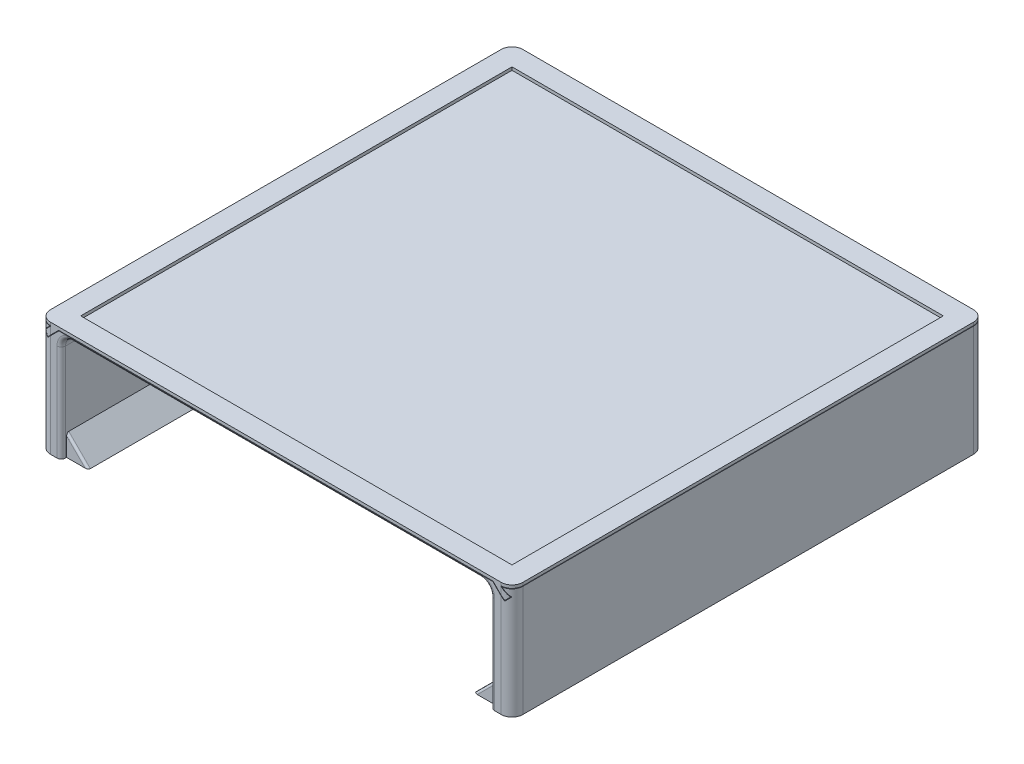
SolidWorks part; units mm, degrees
ref_plane "Front Plane" through (0, 0, 0) normal (0, 0, 1) x (1, 0, 0)
ref_plane "Top Plane" through (0, 0, 0) normal (0, 1, 0) x (1, 0, 0)
ref_plane "Right Plane" through (0, 0, 0) normal (1, 0, 0) x (0, 0, -1)
sketch "Sketch1" plane through (0, 0, 0) normal (0, 0, 1) x (1, 0, 0)
  line L0 (-99.5, -1.5) -> (99.5, -1.5)
  line L1 (-109.5, -51.5) -> (-99.5, -51.5)
  line L2 (-109.5, -51.5) -> (-109.5, 0)
  line L4 (-99.5, -51.5) -> (-99.5, -1.5)
  line L5 (0, -1.5) -> (0, 0) construction
  line L10 (-109.5, 0.2) -> (-104.2343, 0.2)
  line L14 (-100.6988, 0.2) -> (100.6988, 0.2)
  line L15 (0, 0.2) -> (0, 1.6) construction
  line L16 (109.5, 1.6) -> (-109.5, 1.6)
  line L17 (-109.5, 1.6) -> (-109.5, 0.2)
  line L21 (-109.5, 0) -> (-104.7172, 0)
  line L22 (-100.6159, 0) -> (100.6159, 0)
  line L23 (109.5, 1.2) -> (-109.5, 1.2) construction
  line L24 (109.5, 0) -> (104.7172, 0)
  line L28 (109.5, 1.6) -> (109.5, 0.2)
  line L29 (109.5, 0.2) -> (104.2343, 0.2)
  line L33 (99.5, -51.5) -> (99.5, -1.5)
  line L34 (109.5, -51.5) -> (109.5, 0)
  line L35 (109.5, -51.5) -> (99.5, -51.5)
  line L36 (-100.5, 0.2) -> (-100.5, 1.2) construction
  line L37 (-100.6988, 0.2) -> (-105.9494, -5.0506)
  line L38 (-105.9494, -5.0506) -> (-107.7172, -3.2828)
  line L39 (-107.7172, -3.2828) -> (-104.2343, 0.2)
  line L40 (-104.7172, 0) -> (-108, -3.2828)
  line L41 (-108, -3.2828) -> (-105.9494, -5.3335)
  line L42 (-105.9494, -5.3335) -> (-100.6159, 0)
  line L43 (-106.9747, -4.3081) -> (-106.8333, -4.1667) construction
  line L44 (100.6988, 0.2) -> (105.9494, -5.0506)
  line L45 (105.9494, -5.3335) -> (100.6159, 0)
  line L46 (108, -3.2828) -> (105.9494, -5.3335)
  line L47 (105.9494, -5.0506) -> (107.7172, -3.2828)
  line L48 (107.7172, -3.2828) -> (104.2343, 0.2)
  line L49 (104.7172, 0) -> (108, -3.2828)
  point P21 (0, 1.2)
  dimension "D1" = 109.5
  dimension "D5" = 0.2
  dimension "D9" = 0.4
  dimension "MetalSheetGap" = 1
  dimension "D11" = 10
  dimension "MainBoardSize" = 50
  dimension "D13" = 9
  dimension "D3" = 45
  dimension "D4" = 1.5
  dimension "D2" = 2.5
  dimension "D7" = 0.2
  dimension "D8" = 0.2
  dimension "D10" = 3
  dimension "D6" = 1.5
extrude "Boss-Extrude1" add sketch "Sketch1" along normal mid plane 219 contours L4 L0 L33 L35 L34 L24 L49 L46 L45 L22 L42 L41 L40 L21 L2 L1
extrude "Boss-Extrude2" add sketch "Sketch1<4>" along normal mid plane 219 separate body contours L16 L17 L10 L39 L38 L37 L14 L44 L47 L48 L29 L28
sketch "Sketch1<4>" plane through (0, 0, 0) normal (0, 0, 1) x (1, 0, 0) same geometry as "Sketch1"
sketch "Sketch2" plane through (0, 0.2, 0) normal (0, -1, 0) x (1, 0, 0)
  line L1 (-100, -100) -> (100, -100)
  line L2 (-100, -100) -> (-100, 100)
  line L3 (-100, 100) -> (100, 100)
  line L4 (100, -100) -> (100, 100)
  line L5 (-100, -100) -> (100, 100) construction
  line L6 (-100, 100) -> (100, -100) construction
  point P0 (0, 0)
  dimension "D1" = 200
  dimension "D2" = 200
extrude "Cut-Extrude1" cut sketch "Sketch2" against normal through all contours L3 L4 L1 L2
fillet "Fillet1" radius 5 2 edges at (99.5, -1.5, 0) (-99.5, -1.5, 0)
sketch "Sketch3" plane through (0, 0, 0) normal (0, 0, 1) x (1, 0, 0)
  line L1 (-99.5, -1.5) -> (99.5, -1.5)
  line L2 (-99.5, -1.5) -> (-99.5, -51.5)
  line L3 (-99.5, -51.5) -> (99.5, -51.5)
  line L4 (99.5, -1.5) -> (99.5, -51.5)
extrude "Boss-Extrude3" add sketch "Sketch3" along normal mid plane 10
fillet "Fillet2" radius 5 4 edges at (-109.5, -25.75, 109.5) (-109.5, -25.75, -109.5) (109.5, -25.75, -109.5) (109.5, -25.75, 109.5)
sketch "Sketch9" plane through (0, -51.5, 0) normal (0, -1, 0) x (1, 0, 0)
  line L0 (104.5, -109.5) -> (-104.5, -109.5)
  line L1 (-109.5, -104.5) -> (-109.5, 104.5)
  line L2 (-104.5, 109.5) -> (104.5, 109.5)
  line L3 (109.5, 104.5) -> (109.5, -104.5)
  line L5 (-189.5, 189.5) -> (189.5, 189.5)
  line L6 (-189.5, 189.5) -> (-189.5, -189.5)
  line L7 (-189.5, -189.5) -> (189.5, -189.5)
  line L8 (189.5, 189.5) -> (189.5, -189.5)
  line L9 (-189.5, 189.5) -> (189.5, -189.5) construction
  line L10 (-189.5, -189.5) -> (189.5, 189.5) construction
  arc A0 (-104.5, 109.5) -> (-109.5, 104.5) centre (-104.5, 104.5) ccw
  arc A1 (-104.5, 109.5) -> (-109.5, 104.5) centre (-104.5, 104.5) ccw
  arc A2 (109.5, 104.5) -> (104.5, 109.5) centre (104.5, 104.5) ccw
  arc A3 (109.5, 104.5) -> (104.5, 109.5) centre (104.5, 104.5) ccw
  arc A4 (104.5, -109.5) -> (109.5, -104.5) centre (104.5, -104.5) ccw
  arc A5 (104.5, -109.5) -> (109.5, -104.5) centre (104.5, -104.5) ccw
  arc A6 (-109.5, -104.5) -> (-104.5, -109.5) centre (-104.5, -104.5) ccw
  arc A7 (-109.5, -104.5) -> (-104.5, -109.5) centre (-104.5, -104.5) ccw
  point P7 (0, 0)
  line M9 (-99.5, 109.5) -> (-104.5, 109.5)
  arc M10 (-104.5, 109.5) -> (-109.5, 104.5) centre (-104.5, 104.5) ccw
  line M11 (-109.5, 104.5) -> (-109.5, -104.5)
  arc M12 (-109.5, -104.5) -> (-104.5, -109.5) centre (-104.5, -104.5) ccw
  line M13 (-104.5, -109.5) -> (-99.5, -109.5)
  line M17 (99.5, -109.5) -> (104.5, -109.5)
  arc M18 (104.5, -109.5) -> (109.5, -104.5) centre (104.5, -104.5) ccw
  line M19 (109.5, -104.5) -> (109.5, 104.5)
  arc M20 (109.5, 104.5) -> (104.5, 109.5) centre (104.5, 104.5) ccw
  line M21 (104.5, 109.5) -> (99.5, 109.5)
  dimension "D1" = 80
extrude "Cut-Extrude3" cut sketch "Sketch9" against normal through all contours L8 L5 L6 L7 L2 L0 M9 M21 M20 M19 M18 M17 M13 M12 M11 M10 region at (0, -51.5, 184.1401)
fillet "Fillet4" radius 2 10 edges at (-99.5, -29, 109.5) (-98.0355, -2.9645, 109.5) (99.5, -29, 109.5) (98.0355, -2.9645, 109.5) (-99.5, -29, -109.5) (-98.0355, -2.9645, -109.5) (99.5, -29, -109.5) (98.0355, -2.9645, -109.5) (0, -1.5, 109.5) (0, -1.5, -109.5)
fillet "Fillet5" radius 1 10 edges at (-99.5, -29, -5) (-98.0355, -2.9645, -5) (0, -1.5, -5) (98.0355, -2.9645, -5) (-99.5, -29, 5) (-98.0355, -2.9645, 5) (0, -1.5, 5) (98.0355, -2.9645, 5) (99.5, -29, -5) (99.5, -29, 5)
sketch "Sketch6" plane through (0, 0, 0) normal (0, 0, 1) x (1, 0, 0)
  line L0 (-99.5, -51.5) -> (-89.5, -51.5)
  line L1 (-98.5, -51.5) -> (98.5, -51.5) construction
  line L2 (-89.5, -51.5) -> (-99.5, -41.5)
  line L3 (-99.5, -41.5) -> (-99.5, -51.5)
  dimension "D1" = 45
  dimension "D2" = 10
extrude "Boss-Extrude6" add sketch "Sketch6" against normal mid plane 214
fillet "Fillet6" radius 1 2 edges at (-94.5, -46.5, 107) (-94.5, -46.5, -107)
mirror "Mirror1" about plane through (0, 0, 0) normal (1, 0, 0) of "Fillet6", "Boss-Extrude6"
sketch "Sketch10" plane through (0, 0, 0) normal (0, 0, 1) x (1, 0, 0)
  line L1 (10, -17) -> (-10, -17)
  line L2 (10, -17) -> (10, -27)
  line L4 (-10, -17) -> (-10, -27)
  arc A0 (10, -27) -> (-10, -27) centre (0, -27) cw
extrude "Cut-Extrude4" cut sketch "Sketch10" against normal mid plane 4
equation "\"CheckerPatternThickness\"= 0.2mm * 2'How thick the squares the pecies sit on should be"
equation "\"D9@Sketch1\"=\"CheckerPatternThickness\""
equation "\"D2@Sketch2\"=\"D1@Sketch2\""
equation "\"D7@Sketch1\"=\"D5@Sketch1\""
equation "\"D8@Sketch1\"=\"D5@Sketch1\""
